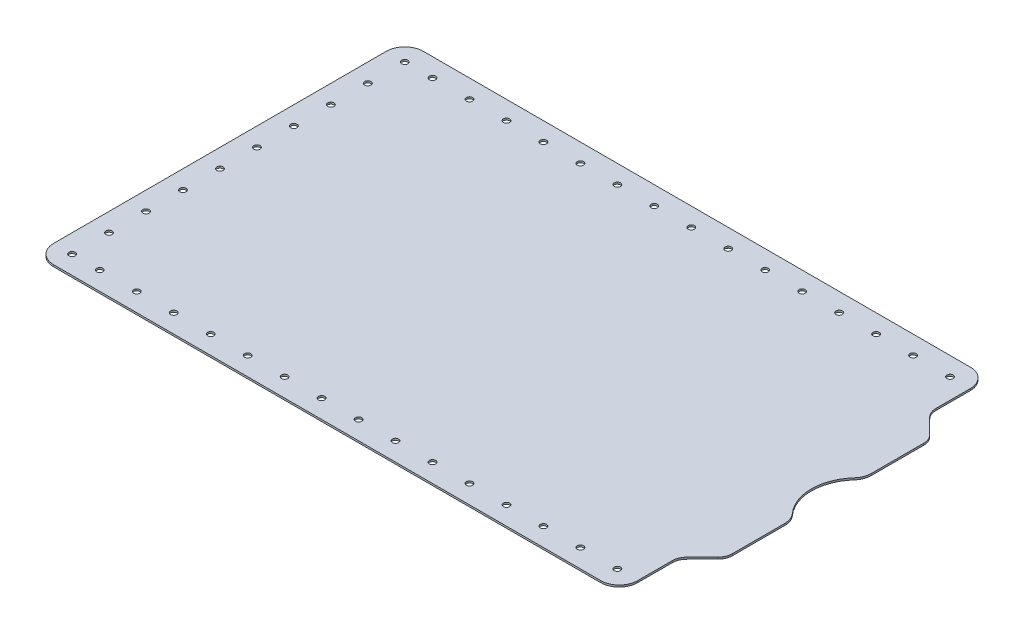
SolidWorks part; units mm, degrees
material "AISI 1020 Steel, Cold Rolled"
ref_plane "Front Plane" through (0, 0, 0) normal (0, 0, 1) x (1, 0, 0)
ref_plane "Top Plane" through (0, 0, 0) normal (0, 1, 0) x (1, 0, 0)
ref_plane "Right Plane" through (0, 0, 0) normal (1, 0, 0) x (0, 0, -1)
sketch "Sketch1" plane through (0, 0, 0) normal (0, 1, 0) x (1, 0, 0)
  line L1 (-164.5, 100) -> (164.5, 100)
  line L2 (-164.5, 100) -> (-164.5, -100)
  line L3 (-164.5, -100) -> (164.5, -100)
  line L4 (164.5, 100) -> (164.5, -100)
  line L5 (-164.5, 100) -> (164.5, -100) construction
  line L6 (-164.5, -100) -> (164.5, 100) construction
  point P0 (0, 0)
  dimension "D1" = 329
  dimension "D2" = 200
extrude "Boss-Extrude1" add sketch "Sketch1" along normal blind 1
sketch "Sketch2" plane through (0, 0, 0) normal (0, -1, 0) x (-1, 0, 0)
  line L0 (-164.5, -55) -> (-151.5, -68)
  line L5 (-164.5, -100) -> (-164.5, 100) construction
  line L6 (-151.5, -68) -> (-151.5, -100)
  line L7 (164.5, -100) -> (-164.5, -100) construction
  line L8 (-151.5, -100) -> (-164.5, -100)
  line L9 (-164.5, -100) -> (-164.5, -55)
  line L10 (-0.55, 0) -> (0.55, 0) construction
  line L11 (-151.5, 100) -> (-164.5, 100)
  line L12 (-151.5, 68) -> (-151.5, 100)
  line L13 (-164.5, 55) -> (-151.5, 68)
  line L14 (-164.5, 100) -> (-164.5, 55)
  dimension "D1" = 13
  dimension "D2" = 45
  dimension "D3" = 32
extrude "Cut-Extrude1" cut sketch "Sketch2" against normal through all
fillet "Fillet1" radius 8 4 edges at (151.5, 0.5, -68) (164.5, 0.5, -55) (151.5, 0.5, 68) (164.5, 0.5, 55)
fillet "Fillet2" radius 10 4 edges at (151.5, 0.5, -100) (-164.5, 0.5, -100) (-164.5, 0.5, 100) (151.5, 0.5, 100)
sketch "Sketch3" plane through (0, 0, 0) normal (0, -1, 0) x (1, 0, 0)
  circle A0 centre (-154.5, -70) radius 1.7 construction
  circle A1 centre (-154.5, -90) radius 1.7 construction
  circle A2 centre (-154.5, 70) radius 1.7 construction
  circle A3 centre (-154.5, 90) radius 1.7 construction
  circle A4 centre (-154.5, -70) radius 1.7
  circle A5 centre (-154.5, -90) radius 1.7
  circle A6 centre (-154.5, 70) radius 1.7
  circle A7 centre (-154.5, 90) radius 1.7
extrude "Cut-Extrude2" cut sketch "Sketch3" against normal through all
hole_wizard "M3 Clearance Hole1" positions "Sketch5" profile "Sketch6" hole size "M3" standard "ANSI Metric" end condition through all
sketch "Sketch5" plane through (0, 0, 0) normal (0, -1, 0) x (-1, 0, 0)
  point P1 (154.5, -70)
  point P11 (154.5, -50)
  point P12 (154.5, -30)
  point P13 (154.5, -10)
  point P14 (154.5, 10)
  point P15 (154.5, 30)
  point P16 (154.5, 50)
  dimension "D2" = 20
  dimension "D1" = 7
sketch "Sketch6" plane through (-154.5, 0, 70) normal (1, 0, 0) x (0, 0, -1)
  line L0 (0, 0) -> (0, 1)
  line L1 (0, 1) -> (1.7, 1)
  line L2 (1.7, 1) -> (1.7, 0.025)
  line L3 (1.7, 0.025) -> (1.725, 0)
  line L5 (1.725, 0) -> (0, 0)
  line L6 (-1.7, 0.025) -> (-1.725, 0) construction
  line L11 (0, -6.35) -> (0, 107.95) construction
  dimension "Thru Hole Dia." = 3.4
  dimension "Thru Hole Depth" = 1
  dimension "Near C'Sink Dia." = 3.45
  dimension "Near C'Sink Angle" = 90
hole_wizard "M3 Clearance Hole2" positions "Sketch7" profile "Sketch8" hole size "M3" standard "ANSI Metric" end condition through all
sketch "Sketch7" plane through (0, 0, 0) normal (0, -1, 0) x (-1, 0, 0)
  line L0 (-151.5, 71.3137) -> (-151.5, 90) construction
  line L1 (-141.5, 100) -> (154.5, 100) construction
  line L2 (-0.55, 0) -> (0.55, 0) construction
  point P0 (-140.5, 90)
  point P14 (-120.5, 90)
  point P15 (-100.5, 90)
  point P16 (-80.5, 90)
  point P17 (-60.5, 90)
  point P18 (-40.5, 90)
  point P19 (-20.5, 90)
  point P20 (-0.5, 90)
  point P21 (19.5, 90)
  point P22 (39.5, 90)
  point P23 (59.5, 90)
  point P24 (79.5, 90)
  point P25 (99.5, 90)
  point P26 (119.5, 90)
  point P27 (139.5, 90)
  point P30 (139.5, -90)
  point P31 (119.5, -90)
  point P32 (99.5, -90)
  point P33 (79.5, -90)
  point P34 (59.5, -90)
  point P35 (39.5, -90)
  point P36 (19.5, -90)
  point P37 (-0.5, -90)
  point P38 (-20.5, -90)
  point P39 (-40.5, -90)
  point P40 (-60.5, -90)
  point P41 (-80.5, -90)
  point P42 (-100.5, -90)
  point P43 (-120.5, -90)
  point P44 (-140.5, -90)
  dimension "D1" = 11
  dimension "D2" = 10
  dimension "D4" = 20
  dimension "D3" = 15
sketch "Sketch8" plane through (140.5, 0, -90) normal (1, 0, 0) x (0, 0, -1)
  line L0 (0, 0) -> (0, 1)
  line L1 (0, 1) -> (1.7, 1)
  line L2 (1.7, 1) -> (1.7, 0.025)
  line L3 (1.7, 0.025) -> (1.725, 0)
  line L5 (1.725, 0) -> (0, 0)
  line L6 (-1.7, 0.025) -> (-1.725, 0) construction
  line L11 (0, -6.35) -> (0, 107.95) construction
  dimension "Thru Hole Dia." = 3.4
  dimension "Thru Hole Depth" = 1
  dimension "Near C'Sink Dia." = 3.45
  dimension "Near C'Sink Angle" = 90
sketch "Sketch9" plane through (0, 0, 0) normal (0, -1, 0) x (-1, 0, 0)
  line L0 (-164.5, 0) -> (-180.5, 0) construction
  line L1 (-164.5, -51.6863) -> (-164.5, 51.6863) construction
  circle A0 centre (-180.5, 0) radius 25
  dimension "D2" = 50
  dimension "D1" = 16
extrude "Cut-Extrude3" cut sketch "Sketch9" against normal blind 10
fillet "Fillet3" radius 10 2 edges at (164.5, 0.5, -19.2094) (164.5, 0.5, 19.2094)
